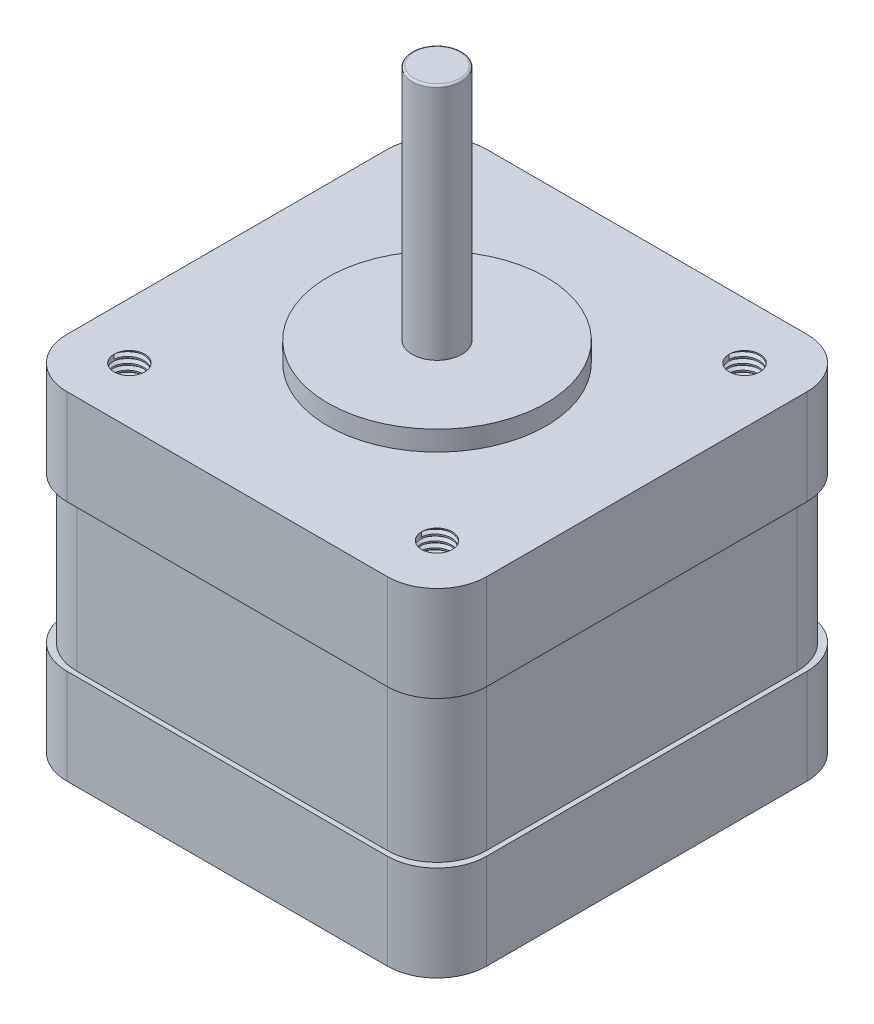
SolidWorks part; units mm, degrees
ref_plane "Front Plane" through (0, 0, 0) normal (0, 0, 1) x (1, 0, 0)
ref_plane "Top Plane" through (0, 0, 0) normal (0, 1, 0) x (1, 0, 0)
ref_plane "Right Plane" through (0, 0, 0) normal (1, 0, 0) x (0, 0, -1)
sketch "Sketch1" plane through (0, 0, 0) normal (0, 1, 0) x (1, 0, 0)
  line L1 (5, 0) -> (37.3, 0)
  line L2 (0, 5) -> (0, 37.3)
  line L3 (5, 42.3) -> (37.3, 42.3)
  line L4 (42.3, 5) -> (42.3, 37.3)
  arc A0 (5, 0) -> (0, 5) centre (5, 5) cw
  arc A1 (37.3, 0) -> (42.3, 5) centre (37.3, 5) ccw
  arc A2 (37.3, 42.3) -> (42.3, 37.3) centre (37.3, 37.3) cw
  arc A3 (0, 37.3) -> (5, 42.3) centre (5, 37.3) cw
  point P7 (0, 0)
  point P12 (42.3, 42.3)
  point P15 (0, 42.3)
  dimension "D3" = 5
  dimension "D1" = 42.3
  dimension "D2" = 42.3
extrude "Boss-Extrude1" add sketch "Sketch1" along normal blind 9.6
sketch "Sketch2" plane through (0, 9.6, 0) normal (0, 1, 0) x (1, 0, 0)
  line L0 (0, 37.3) -> (0, 5) construction
  line L1 (5.5, 0.4967) -> (36.8, 0.4967)
  line L2 (0.5, 5.4967) -> (0.5, 36.8)
  line L3 (5.5, 41.8) -> (36.8, 41.8)
  line L4 (41.8, 5.4967) -> (41.8, 36.8)
  line L5 (37.3, 42.3) -> (5, 42.3) construction
  line L6 (42.3, 5) -> (42.3, 37.3) construction
  line L7 (5, 0) -> (37.3, 0) construction
  arc A0 (5.5, 0.4967) -> (0.5, 5.4967) centre (5.5, 5.4967) cw
  arc A1 (36.8, 0.4967) -> (41.8, 5.4967) centre (36.8, 5.4967) ccw
  arc A2 (36.8, 41.8) -> (41.8, 36.8) centre (36.8, 36.8) cw
  arc A3 (0.5, 36.8) -> (5.5, 41.8) centre (5.5, 36.8) cw
  dimension "D5" = 5
  dimension "D1" = 0.5
  dimension "D2" = 0.5
  dimension "D3" = 0.5
  dimension "D4" = 0.4967
extrude "Boss-Extrude2" add sketch "Sketch2" along normal blind 14.8
sketch "Sketch3" plane through (0, 24.4, 0) normal (0, 1, 0) x (1, 0, 0)
  line L0 (0, 37.3) -> (0, 5) construction
  line L1 (5, 42.3) -> (37.3, 42.3)
  line L2 (0, 37.3) -> (0, 5)
  line L3 (5, 0) -> (37.3, 0)
  line L4 (42.3, 37.3) -> (42.3, 5)
  line L5 (37.3, 42.3) -> (5, 42.3) construction
  line L7 (5.5, 0.4967) -> (36.8, 0.4967) construction
  line L8 (41.8, 5.4967) -> (41.8, 36.8) construction
  arc A0 (37.3, 42.3) -> (42.3, 37.3) centre (37.3, 37.3) cw
  arc A1 (37.3, 0) -> (42.3, 5) centre (37.3, 5) ccw
  arc A2 (0, 5) -> (5, 0) centre (5, 5) ccw
  arc A3 (5, 42.3) -> (0, 37.3) centre (5, 37.3) ccw
  point P10 (42.3, 42.3)
  point P15 (0, 0)
  point P18 (0, 42.3)
  dimension "D3" = 5
  dimension "D4" = 0.4967
  dimension "D1" = 42.3
  dimension "D2" = 42.3
  dimension "D5" = 0.5
extrude "Boss-Extrude3" add sketch "Sketch3" along normal blind 9.6
sketch "Sketch4" plane through (0, 34, 0) normal (0, 1, 0) x (1, 0, 0)
  line L0 (21.15, 42.3) -> (21.15, 0) construction
  line L1 (37.3, 42.3) -> (5, 42.3) construction
  line L2 (5, 0) -> (37.3, 0) construction
  line L3 (0, 21.15) -> (42.3, 21.15) construction
  line L4 (0, 37.3) -> (0, 5) construction
  line L5 (42.3, 5) -> (42.3, 37.3) construction
  circle A0 centre (5.65, 36.65) radius 1.55
  circle A1 centre (36.65, 36.65) radius 1.55
  circle A2 centre (5.65, 5.65) radius 1.55
  circle A3 centre (36.65, 5.65) radius 1.55
  point P14 (21.15, 21.15)
  dimension "D2" = 15.5
  dimension "D3" = 3.1
  dimension "D1" = 15.5
extrude "Cut-Extrude1" cut sketch "Sketch4" against normal blind 4.5
thread "MinColWidth_OnTracking2" pitch 0.6 method cut profile "HeaderRowsCount2" start angle 0, offset 0, length 4.5, pitch 0.6, diameter 3.1
ref_plane "Plane2" through (4.1, 34, -36.65) normal (0, 0, 1) x (-1, 0, 0)
sketch "HeaderRowsCount2" plane through (4.1, 34, -36.65) normal (0, 0, 1) x (-1, 0, 0)
  line L0 (0, 0) -> (0, 0.6) construction
  line L1 (0, 0) -> (0.3248, 0.1875)
  line L2 (0.3248, 0.1875) -> (0.3248, 0.2625)
  line L3 (0.3248, 0.2625) -> (0, 0.45)
  line L4 (0.3248, 0.225) -> (0, 0.225) construction
  line L11 (0, 0) -> (0, 0.45)
  point P2 (0, 0)
  dimension "Pitch" = 0.6
  dimension "Profile_Angle" = 60
  dimension "Profile_Land" = 0.075
  dimension "Profile_Height" = 0.3248
thread "MinColWidth_OnTracking3" pitch 0.6 method cut profile "HeaderRowsCount3" start angle 0, offset 0, length 4.5, pitch 0.6, diameter 3.1
ref_plane "Plane3" through (35.1, 34, -36.65) normal (0, 0, 1) x (-1, 0, 0)
sketch "HeaderRowsCount3" plane through (35.1, 34, -36.65) normal (0, 0, 1) x (-1, 0, 0)
  line L0 (0, 0) -> (0, 0.6) construction
  line L1 (0, 0) -> (0.3248, 0.1875)
  line L2 (0.3248, 0.1875) -> (0.3248, 0.2625)
  line L3 (0.3248, 0.2625) -> (0, 0.45)
  line L4 (0.3248, 0.225) -> (0, 0.225) construction
  line L11 (0, 0) -> (0, 0.45)
  point P2 (0, 0)
  dimension "Pitch" = 0.6
  dimension "Profile_Angle" = 60
  dimension "Profile_Land" = 0.075
  dimension "Profile_Height" = 0.3248
thread "MinColWidth_OnTracking4" pitch 0.6 method cut profile "HeaderRowsCount4" start angle 0, offset 0, length 4.5, pitch 0.6, diameter 3.1
ref_plane "Plane4" through (4.1, 34, -5.65) normal (0, 0, 1) x (-1, 0, 0)
sketch "HeaderRowsCount4" plane through (4.1, 34, -5.65) normal (0, 0, 1) x (-1, 0, 0)
  line L0 (0, 0) -> (0, 0.6) construction
  line L1 (0, 0) -> (0.3248, 0.1875)
  line L2 (0.3248, 0.1875) -> (0.3248, 0.2625)
  line L3 (0.3248, 0.2625) -> (0, 0.45)
  line L4 (0.3248, 0.225) -> (0, 0.225) construction
  line L11 (0, 0) -> (0, 0.45)
  point P2 (0, 0)
  dimension "Pitch" = 0.6
  dimension "Profile_Angle" = 60
  dimension "Profile_Land" = 0.075
  dimension "Profile_Height" = 0.3248
thread "MinColWidth_OnTracking5" pitch 0.6 method cut profile "HeaderRowsCount5" start angle 0, offset 0, length 4.5, pitch 0.6, diameter 3.1
ref_plane "Plane5" through (35.1, 34, -5.65) normal (0, 0, 1) x (-1, 0, 0)
sketch "HeaderRowsCount5" plane through (35.1, 34, -5.65) normal (0, 0, 1) x (-1, 0, 0)
  line L0 (0, 0) -> (0, 0.6) construction
  line L1 (0, 0) -> (0.3248, 0.1875)
  line L2 (0.3248, 0.1875) -> (0.3248, 0.2625)
  line L3 (0.3248, 0.2625) -> (0, 0.45)
  line L4 (0.3248, 0.225) -> (0, 0.225) construction
  line L11 (0, 0) -> (0, 0.45)
  point P2 (0, 0)
  dimension "Pitch" = 0.6
  dimension "Profile_Angle" = 60
  dimension "Profile_Land" = 0.075
  dimension "Profile_Height" = 0.3248
sketch "Sketch18" plane through (0, 34, 0) normal (0, 1, 0) x (1, 0, 0)
  line L0 (0, 21.15) -> (42.3, 21.15) construction
  line L1 (0, 37.3) -> (0, 5) construction
  line L2 (42.3, 5) -> (42.3, 37.3) construction
  line L3 (21.15, 42.3) -> (21.15, 0) construction
  line L4 (37.3, 42.3) -> (5, 42.3) construction
  line L5 (5, 0) -> (37.3, 0) construction
  circle A0 centre (21.15, 21.15) radius 11
  dimension "D1" = 22
extrude "Boss-Extrude4" add sketch "Sketch18" along normal blind 2
sketch "Sketch19" plane through (0, 36, 0) normal (0, 1, 0) x (1, 0, 0)
  circle A0 centre (21.15, 21.15) radius 2.5
  circle A1 centre (21.15, 21.15) radius 11 construction
  dimension "D1" = 5
extrude "Boss-Extrude5" add sketch "Sketch19" along normal blind 24
fillet "Fillet1" radius 0.2 1 edges at (21.15, 60, -18.65)
